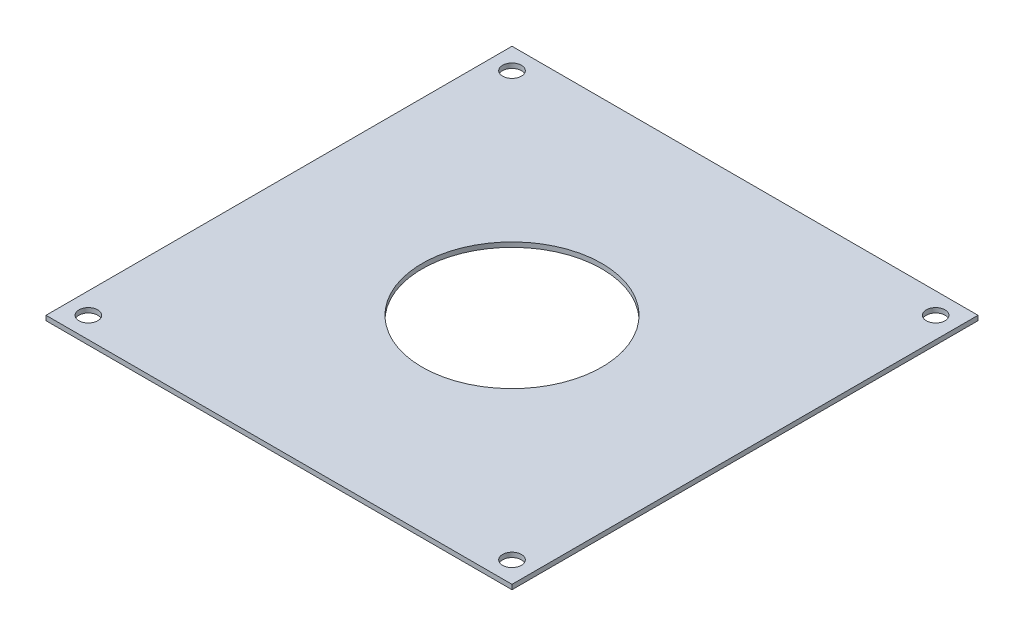
SolidWorks part; units mm, degrees
ref_plane "Front Plane" through (0, 0, 0) normal (0, 0, 1) x (1, 0, 0)
ref_plane "Top Plane" through (0, 0, 0) normal (0, 1, 0) x (1, 0, 0)
ref_plane "Right Plane" through (0, 0, 0) normal (1, 0, 0) x (0, 0, -1)
sketch "Sketch1" plane through (0, 0, 0) normal (0, 1, 0) x (1, 0, 0)
  line L1 (-49.3914, -49.3914) -> (49.3914, -49.3914)
  line L2 (-49.3914, -49.3914) -> (-49.3914, 49.3914)
  line L3 (-49.3914, 49.3914) -> (49.3914, 49.3914)
  line L4 (49.3914, -49.3914) -> (49.3914, 49.3914)
  line L5 (-49.3914, -49.3914) -> (49.3914, 49.3914) construction
  line L6 (-49.3914, 49.3914) -> (49.3914, -49.3914) construction
  point P0 (0, 0)
  dimension "D1" = 139.7
extrude "Boss-Extrude1" add sketch "Sketch1" along normal blind 1
sketch "Sketch3" plane through (0, 0, 0) normal (0, 1, 0) x (1, 0, 0)
  line L0 (-49.3914, -49.3914) -> (49.3914, 49.3914) construction
  line L1 (-44.9013, 44.9013) -> (44.9013, -44.9013) construction
  circle A0 centre (44.9013, 44.9013) radius 2
  circle A1 centre (44.9013, -44.9013) radius 2
  circle A2 centre (-44.9013, -44.9013) radius 2
  circle A3 centre (-44.9013, 44.9013) radius 2
  point P15 (0, 0)
  dimension "D3" = 4
  dimension "D2" = 127
  dimension "D1" = 4
extrude "Cut-Extrude2" cut sketch "Sketch3" along normal through all
sketch "Sketch4" plane through (0, 0, 0) normal (0, 1, 0) x (1, 0, 0)
  circle A0 centre (0, 0) radius 19.05 construction
  circle A1 centre (0, 0) radius 19.05
extrude "Cut-Extrude3" cut sketch "Sketch4" along normal through all
equation "\"D1@Boss-Extrude1\"=1mm"
equation "\"D3@Sketch3\"=4mm"
